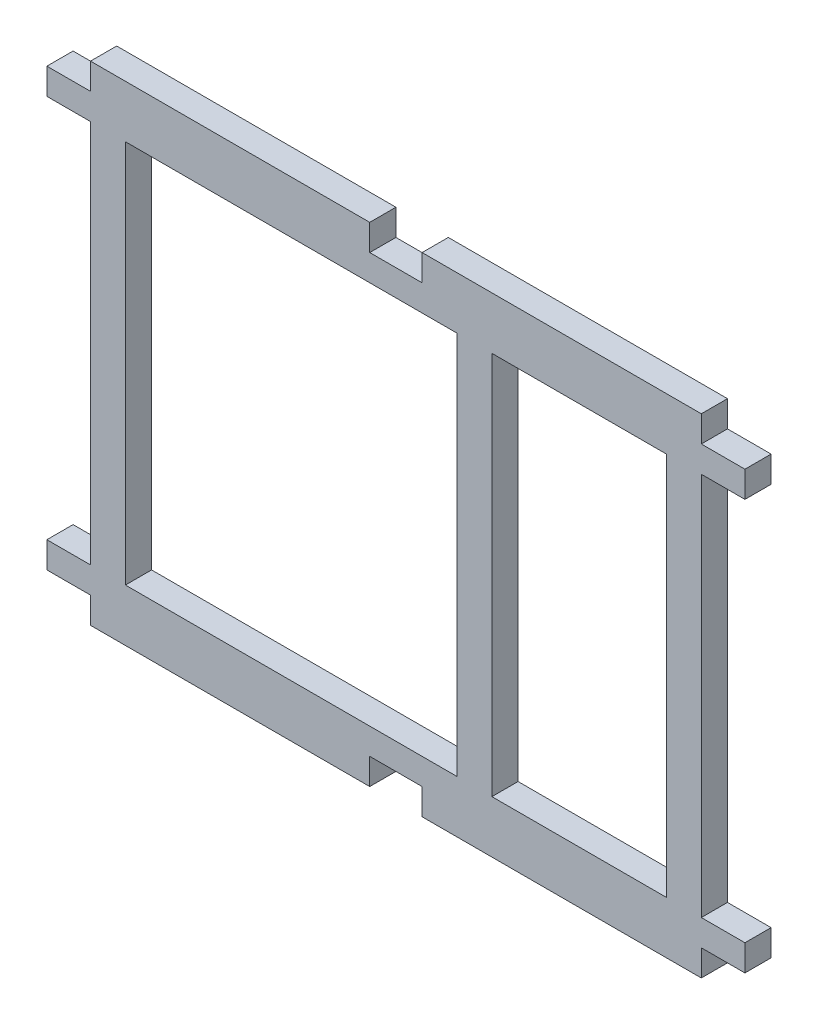
SolidWorks part; units mm, degrees
material "Custom Plastic"
ref_plane "Front Plane" through (0, 0, 0) normal (0, 0, 1) x (1, 0, 0)
ref_plane "Top Plane" through (0, 0, 0) normal (0, 1, 0) x (1, 0, 0)
ref_plane "Right Plane" through (0, 0, 0) normal (1, 0, 0) x (0, 0, -1)
sketch "Sketch1" plane through (0, 0, 0) normal (0, 0, 1) x (1, 0, 0)
  line L0 (-41.2824, 37.1909) -> (-36.2824, 37.1909)
  line L1 (-36.2824, 37.1909) -> (-36.2824, -6.8091)
  line L2 (-36.2824, -6.8091) -> (-41.2824, -6.8091)
  line L3 (-41.2824, -6.8091) -> (-41.2824, -9.8091)
  line L4 (-41.2824, -9.8091) -> (-36.2824, -9.8091)
  line L5 (-36.2824, -9.8091) -> (-36.2824, -12.8091)
  line L6 (-36.2824, -12.8091) -> (-4.2824, -12.8091)
  line L7 (-4.2824, -12.8091) -> (-4.2824, -9.8091)
  line L8 (-4.2824, -9.8091) -> (1.7176, -9.8091)
  line L9 (1.7176, -9.8091) -> (1.7176, -12.8091)
  line L10 (1.7176, -12.8091) -> (33.7176, -12.8091)
  line L11 (33.7176, -12.8091) -> (33.7176, -9.8091)
  line L12 (33.7176, -9.8091) -> (38.7176, -9.8091)
  line L13 (38.7176, -9.8091) -> (38.7176, -6.8091)
  line L14 (38.7176, -6.8091) -> (33.7176, -6.8091)
  line L15 (33.7176, -6.8091) -> (33.7176, 37.1909)
  line L16 (33.7176, 37.1909) -> (38.7176, 37.1909)
  line L17 (38.7176, 37.1909) -> (38.7176, 40.1909)
  line L18 (38.7176, 40.1909) -> (33.7176, 40.1909)
  line L19 (33.7176, 40.1909) -> (33.7176, 43.1909)
  line L20 (33.7176, 43.1909) -> (1.7176, 43.1909)
  line L21 (1.7176, 43.1909) -> (1.7176, 40.1909)
  line L22 (1.7176, 40.1909) -> (-4.2824, 40.1909)
  line L23 (-4.2824, 40.1909) -> (-4.2824, 43.1909)
  line L24 (-4.2824, 43.1909) -> (-36.2824, 43.1909)
  line L25 (-36.2824, 43.1909) -> (-36.2824, 40.1909)
  line L26 (-36.2824, 40.1909) -> (-41.2824, 40.1909)
  line L27 (-41.2824, 40.1909) -> (-41.2824, 37.1909)
  line L28 (-36.2824, -6.8091) -> (33.7176, -6.8091) construction
  line L29 (-36.2824, 37.1909) -> (33.7176, 37.1909) construction
  line L30 (-32.2824, -6.8091) -> (-32.2824, 37.1909)
  line L31 (-32.2824, 37.1909) -> (5.7176, 37.1909)
  line L32 (5.7176, 37.1909) -> (5.7176, -6.8091)
  line L33 (5.7176, -6.8091) -> (-32.2824, -6.8091)
  line L34 (9.7176, -6.8091) -> (9.7176, 37.1909)
  line L35 (9.7176, 37.1909) -> (29.7176, 37.1909)
  line L36 (29.7176, 37.1909) -> (29.7176, -6.8091)
  line L37 (29.7176, -6.8091) -> (9.7176, -6.8091)
  dimension "D1" = 50
  dimension "D2" = 3
  dimension "D3" = 3
  dimension "D4" = 80
  dimension "D5" = 4
  dimension "D6" = 6
  dimension "D7" = 5
  dimension "D8" = 4
  dimension "D9" = 4
  dimension "D10" = 20
extrude "Boss-Extrude1" add sketch "Sketch1" along normal blind 3
